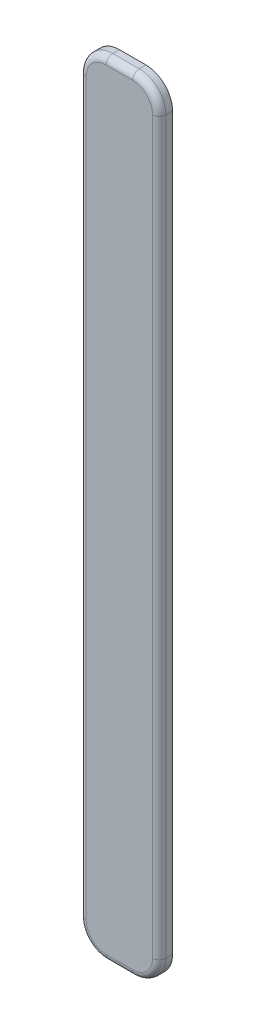
SolidWorks part; units mm, degrees
ref_plane "Спереди" through (0, 0, 0) normal (0, 0, 1) x (1, 0, 0)
ref_plane "Сверху" through (0, 0, 0) normal (0, 1, 0) x (1, 0, 0)
ref_plane "Справа" through (0, 0, 0) normal (1, 0, 0) x (0, 0, -1)
sketch "Эскиз1" plane through (0, 0, 0) normal (0, 0, 1) x (1, 0, 0)
  line L1 (0, 0) -> (12, 0)
  line L2 (0, 0) -> (0, 118)
  line L3 (0, 118) -> (12, 118)
  line L4 (12, 0) -> (12, 118)
  dimension "D1" = 12
  dimension "D2" = 118
extrude "Бобышка-Вытянуть1" add sketch "Эскиз1" along normal blind 2
fillet "Скругление1" radius 4 4 edges at (0, 0, 1) (12, 0, 1) (0, 118, 1) (12, 118, 1)
fillet "Скругление2" radius 1 8 edges at (1.1716, 116.8284, 2) (6, 118, 2) (10.8284, 116.8284, 2) (12, 59, 2) (10.8284, 1.1716, 2) (6, 0, 2) (1.1716, 1.1716, 2) (0, 59, 2)
